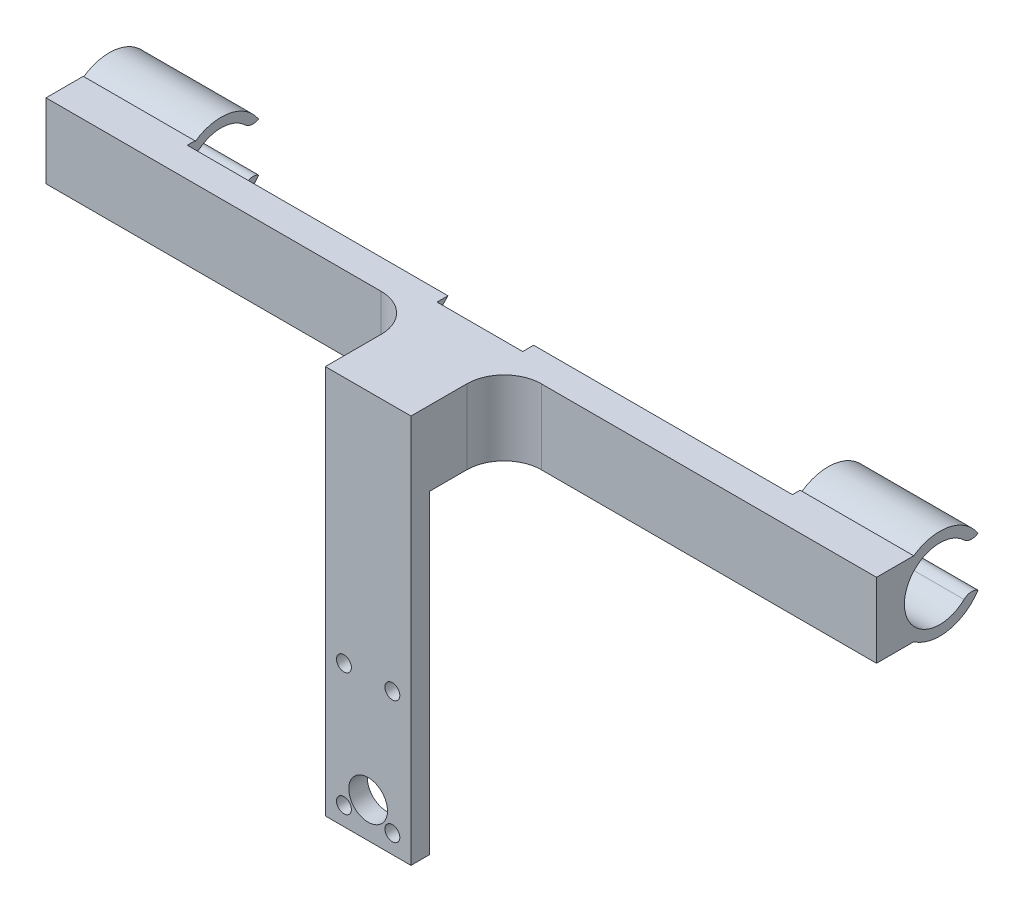
SolidWorks part; units mm, degrees
note: The reader was unsure of these and kept them because the rebuilt part matched: shared geometry of "Sketch3<3>", "Sketch4<3>".
ref_plane "Front Plane" through (0, 0, 0) normal (0, 0, 1) x (1, 0, 0)
ref_plane "Top Plane" through (0, 0, 0) normal (0, 1, 0) x (1, 0, 0)
ref_plane "Right Plane" through (0, 0, 0) normal (1, 0, 0) x (0, 0, -1)
sketch "Sketch1" plane through (0, 0, 0) normal (0, 0, 1) x (1, 0, 0)
  line L0 (0, -21.5) -> (0, -18.5)
  line L1 (-11.5, 21.5) -> (11.5, 21.5)
  line L2 (-11.5, 21.5) -> (-11.5, -21.5)
  line L3 (-11.5, -21.5) -> (11.5, -21.5)
  line L4 (11.5, 21.5) -> (11.5, -21.5)
  line L5 (0, -21.5) -> (0, 21.5) construction
  line L6 (-11.5, 0) -> (11.5, 0) construction
  line L7 (-6.5, 16.5) -> (6.5, 16.5)
  line L8 (-6.5, 16.5) -> (-6.5, -16.5)
  line L9 (-6.5, -16.5) -> (6.5, -16.5)
  line L10 (6.5, 16.5) -> (6.5, -16.5)
  line L11 (0, -16.5) -> (0, 16.5) construction
  line L12 (-6.5, 0) -> (6.5, 0) construction
  line L13 (0, -18.5) -> (0, -12)
  line L14 (0, -12) -> (0, 83)
  line L16 (-11.5, 21.5) -> (11.5, 21.5)
  line L17 (-11.5, 21.5) -> (-11.5, 83)
  line L18 (-11.5, 83) -> (11.5, 83)
  line L19 (11.5, 21.5) -> (11.5, 83)
  circle A0 centre (-6.5, 16.5) radius 2
  circle A1 centre (6.5, 16.5) radius 2
  circle A2 centre (-6.5, -16.5) radius 2
  circle A3 centre (6.5, -16.5) radius 2
  circle A4 centre (0, -12) radius 5.2
  point P0 (0, 0)
  point P4 (0, 0)
  dimension "D5" = 61.5
  dimension "D1" = 43
  dimension "D2" = 23
  dimension "D3" = 33
  dimension "D4" = 13
  dimension "D6" = 23
extrude "Boss-Extrude1" add sketch "Sketch1" along normal blind 5
sketch "Sketch2" plane through (0, 0, 0) normal (0, 0, -1) x (-1, 0, 0)
  line L1 (11.5, 83) -> (-11.5, 83)
  line L2 (11.5, 83) -> (11.5, 63)
  line L3 (11.5, 63) -> (-11.5, 63)
  line L4 (-11.5, 83) -> (-11.5, 63)
  line L5 (-11.5, 83) -> (-11.5, -21.5) construction
  dimension "D1" = 20
  dimension "D2" = 23
extrude "Boss-Extrude2" add sketch "Sketch2" along normal blind 20
sketch "Sketch3" plane through (0, 0, -20) normal (0, 0, -1) x (-1, 0, 0)
  line L1 (-11.5, 83) -> (-111.5, 83)
  line L2 (-11.5, 83) -> (-11.5, 63)
  line L3 (-11.5, 63) -> (-111.5, 63)
  line L4 (-111.5, 83) -> (-111.5, 63)
  line L5 (11.5, 83) -> (111.5, 83)
  line L6 (11.5, 83) -> (11.5, 63)
  line L7 (11.5, 63) -> (111.5, 63)
  line L8 (111.5, 83) -> (111.5, 63)
  line L9 (-11.5, 83) -> (11.5, 83)
  line L10 (-11.5, 83) -> (-11.5, 63)
  line L11 (-11.5, 63) -> (11.5, 63)
  line L12 (11.5, 83) -> (11.5, 63)
  line M1 (11.5, 63) -> (11.5, 83)
  line M2 (11.5, 83) -> (-11.5, 83)
  line M3 (-11.5, 83) -> (-11.5, 63)
  line M4 (-11.5, 63) -> (11.5, 63)
  dimension "D1" = 20
  dimension "D2" = 100
  dimension "D3" = 20
  dimension "D4" = 100
  dimension "D5" = 20
  dimension "D6" = 23
extrude "Boss-Extrude3" add sketch "Sketch3" along normal blind 5 contours M4 M1 M2 M3
extrude "Boss-Extrude4" add sketch "Sketch3<3>" along normal blind 10 contours L1 L4 L3 M3 | L8 L5 L7 M1
sketch "Sketch3<3>" plane through (0, 0, -20) normal (0, 0, -1) x (-1, 0, 0) same geometry as "Sketch3"
sketch "Sketch4" plane through (111.5, 0, 0) normal (1, 0, 0) x (0, 0, -1)
  line L0 (30, 73) -> (37, 73)
  line L1 (30, 73) -> (27.5, 73)
  line L2 (30, 83) -> (30, 63) construction
  line L3 (37, 73) -> (47.2561, 79.6191)
  line L4 (47.2561, 79.6191) -> (47.2561, 66.3809)
  line L5 (47.2561, 66.3809) -> (37, 73)
  circle A0 centre (37, 73) radius 9.5
  circle A1 centre (37, 73) radius 12.2066
  line M3 (30, 63) -> (30, 83)
extrude "Boss-Extrude5" add sketch "Sketch4" against normal blind 30 contours L3 A1 A0 M3 | A1 L5 A0 M3
sketch "Sketch5" plane through (-111.5, 0, 0) normal (-1, 0, 0) x (0, 0, 1)
  line L0 (-30, 73) -> (-27.5, 73)
  line L1 (-30, 83) -> (-30, 63) construction
  line L5 (-30, 73) -> (-37.0054, 73)
  line L11 (-37.0054, 73) -> (-47.0864, 79.5095)
  line L12 (-44.982, 78.1514) -> (-47.2561, 79.6191) construction
  line L13 (-37.0054, 73) -> (-47.0864, 66.4905)
  line L14 (-47.2561, 66.3809) -> (-44.982, 67.8486) construction
  circle A4 centre (-37.0054, 73) radius 9.5054
  circle A5 centre (-37.0054, 73) radius 12
  line M3 (-30, 83) -> (-30, 63)
extrude "Boss-Extrude6" add sketch "Sketch5" against normal blind 30 contours A5 L11 A4 M3 | L13 A5 A4 M3
fillet "Fillet1" radius 10 2 edges at (-11.5, 73, -20) (11.5, 73, -20)
extrude "Cut-Extrude1" cut sketch "Sketch4<3>" against normal blind 300 contours L1 A0 M3 | A0 L1 M3
sketch "Sketch4<3>" plane through (111.5, 0, 0) normal (1, 0, 0) x (0, 0, -1) same geometry as "Sketch4"
sketch "Sketch6" plane through (-81.5, 0, 0) normal (1, 0, 0) x (0, 0, -1)
  circle A1 centre (37.0054, 73) radius 13.5
extrude "Cut-Extrude2" cut sketch "Sketch6" along normal blind 162.5
fillet "Fillet5" radius 3 4 edges at (96.5, 67.8486, -44.982) (-96.5, 67.8437, -44.9907) (-96.5, 78.1563, -44.9907) (96.5, 78.1514, -44.982)
